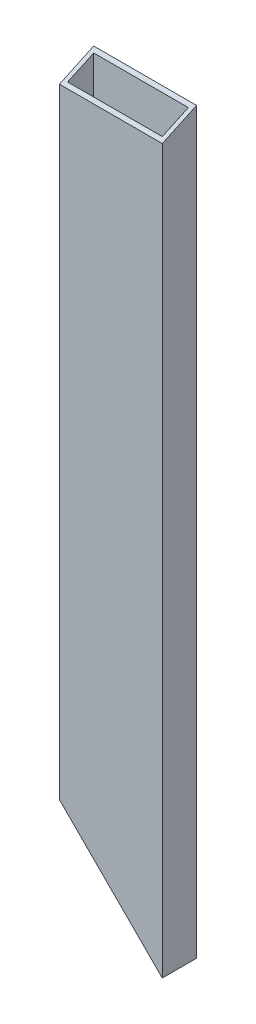
SolidWorks part; units mm, degrees
note: '?' marks a value the reader was unsure of.
material "A500"
ref_plane "Front Plane" through (0, 0, 0) normal (0, 0, 1) x (1, 0, 0)
ref_plane "Top Plane" through (0, 0, 0) normal (0, 1, 0) x (1, 0, 0)
ref_plane "Right Plane" through (0, 0, 0) normal (1, 0, 0) x (0, 0, -1)
sketch "Sketch1" plane through (0, 0, 0) normal (0, 1, 0) x (1, 0, 0)
  line L0 (0, 9.652) -> (0, 12.7) construction
  line L1 (-38.1, 12.7) -> (38.1, 12.7)
  line L2 (-38.1, 12.7) -> (-38.1, -12.7)
  line L3 (-38.1, -12.7) -> (38.1, -12.7)
  line L4 (38.1, 12.7) -> (38.1, -12.7)
  line L5 (-35.052, 9.652) -> (35.052, 9.652)
  line L6 (-35.052, 9.652) -> (-35.052, -9.652)
  line L7 (-35.052, -9.652) -> (35.052, -9.652)
  line L8 (35.052, 9.652) -> (35.052, -9.652)
  line L9 (35.052, 0) -> (38.1, 0) construction
  line L10 (0, -9.652) -> (0, -12.7) construction
  line L11 (-35.052, 0) -> (-38.1, 0) construction
  line L12 (0, 9.652) -> (0, 0) construction
  line L13 (0, 0) -> (-35.052, 0) construction
  dimension "D1" = 76.2
  dimension "D2" = 25.4
  dimension "D3" = 3.048
extrude "Boss-Extrude1" add sketch "Sketch1" along normal up to vertex (503 mm away)
ref_plane "Plane1" through (0, 0, 0) normal (0, 0, 1) x (1, 0, 0)
sketch "Sketch2" plane through (0, 0, 0) normal (0, 0, 1) x (1, 0, 0)
  line L0 (0, 0) -> (0, 503) construction
  line L1 (-38.1, 503) -> (38.1, 503) construction
  line L2 (0, 251.5) -> (-38.1, 251.5) construction
  line L3 (-38.1, 503) -> (-38.1, 0) construction
  line L4 (0, 251.5) -> (38.1, 251.5) construction
  line L5 (38.1, 503) -> (38.1, 0) construction
ref_axis "Axis1" through (0, 503, 0) along (0, -1, 0)?
sketch "Sketch3" plane through (0, 0, 0) normal (0, -1, 0) x (1, 0, 0)
  line L0 (35.052, 9.652) -> (35.052, -9.652) construction
  line L1 (35.052, 9.652) -> (35.052, -9.652)
  line L2 (35.052, -9.652) -> (-35.052, -9.652) construction
  line L3 (35.052, -9.652) -> (-35.052, -9.652)
  line L4 (-38.1, 12.7) -> (-38.1, -12.7)
  line L5 (-38.1, -12.7) -> (38.1, -12.7)
  line L6 (38.1, -12.7) -> (38.1, 12.7)
  line L7 (38.1, 12.7) -> (-38.1, 12.7)
  line L8 (-38.1, 12.7) -> (-38.1, -12.7)
  line L9 (-38.1, -12.7) -> (38.1, -12.7)
  line L10 (38.1, -12.7) -> (38.1, 12.7)
  line L11 (38.1, 12.7) -> (-38.1, 12.7)
  line L12 (-35.052, 9.652) -> (35.052, 9.652) construction
  line L13 (-35.052, 9.652) -> (35.052, 9.652)
  line L14 (-35.052, -9.652) -> (-35.052, 9.652) construction
  line L15 (-35.052, -9.652) -> (-35.052, 9.652)
  dimension "D1" = 0
extrude "Boss-Extrude2" add sketch "Sketch3" along normal blind 38.1
sketch "Sketch4" plane through (0, 503, 0) normal (0, 1, 0) x (1, 0, 0)
  line L0 (35.052, -9.652) -> (35.052, 9.652) construction
  line L1 (35.052, -9.652) -> (35.052, 9.652)
  line L2 (-35.052, -9.652) -> (35.052, -9.652) construction
  line L3 (-35.052, -9.652) -> (35.052, -9.652)
  line L4 (-38.1, 12.7) -> (-38.1, -12.7)
  line L5 (-38.1, -12.7) -> (38.1, -12.7)
  line L6 (38.1, -12.7) -> (38.1, 12.7)
  line L7 (38.1, 12.7) -> (-38.1, 12.7)
  line L8 (-38.1, 12.7) -> (-38.1, -12.7)
  line L9 (-38.1, -12.7) -> (38.1, -12.7)
  line L10 (38.1, -12.7) -> (38.1, 12.7)
  line L11 (38.1, 12.7) -> (-38.1, 12.7)
  line L12 (35.052, 9.652) -> (-35.052, 9.652) construction
  line L13 (35.052, 9.652) -> (-35.052, 9.652)
  line L14 (-35.052, 9.652) -> (-35.052, -9.652) construction
  line L15 (-35.052, 9.652) -> (-35.052, -9.652)
  dimension "D1" = 0
sketch "Sketch5" plane through (0, 0.0477, 0) normal (0, 0, -1) x (0, -1, 0)
  line L0 (-54.5398, 54.4851) -> (43.4084, -43.2794)
  line L1 (0, 25.4) -> (-54.5398, 54.4851) construction
  line L2 (0, 500) -> (0, 0) construction
  line L3 (-54.5398, 54.4851) -> (-25.3523, 0) construction
  line L4 (0.0477, 0) -> (-502.9523, 0) construction
  line L6 (-54.5398, 54.4851) -> (36.5906, 145.7868)
  line L7 (36.5906, 145.7868) -> (134.5388, 48.0222)
  line L8 (134.5388, 48.0222) -> (43.4084, -43.2794)
  dimension "D1" = 25.4
  dimension "D2" = 25.4
extrude "Cut-Extrude1" cut sketch "Sketch5" against normal through all both and the other way through all
extrude "Boss-Extrude3" add sketch "Sketch4" along normal blind 38.1
sketch "Sketch7" plane through (38.1, 0, 0) normal (1, 0, 0) x (0, 0, -1)
  line L3 (0, 503) -> (-19.7823, 519.7329) construction
  line L4 (0, 503) -> (-152.7, 632.1616) construction
  line L5 (0, 503) -> (0, 477.0899) construction
  line L6 (0, 0) -> (0, 503) construction
  line L7 (0, 477.0899) -> (0, 503) construction
  line L8 (0, 503) -> (-33.8727, 487.2863)
  line L9 (0, 503) -> (-19.7823, 519.7329) construction
  line L14 (-33.8727, 487.2863) -> (-19.7823, 519.7329) construction
  line L15 (-33.8727, 487.2863) -> (0, 477.0899) construction
  line L16 (0, 503) -> (53.5924, 527.8618)
  line L17 (53.5924, 527.8618) -> (15.9068, 602.5414)
  line L18 (15.9068, 602.5414) -> (-33.9677, 580.6727)
  line L19 (-33.9677, 580.6727) -> (-33.8727, 487.2863)
extrude "Cut-Extrude4" cut sketch "Sketch7" against normal through all
equation "\"tubeMainWidth\"= 76.2mm"
equation "\"tubeSecondWidth\"= 25.4mm"
equation "\"tubeThickness\"= 3.048mm"
equation "\"halfMainWidthOfTubing\"= (\"tubeMainWidth\"/2)"
equation "\"D1@Sketch1\"=\"tubeMainWidth\""
equation "\"D2@Sketch1\"=\"tubeSecondWidth\""
equation "\"D3@Sketch1\"=\"tubeThickness\""
equation "\"D1@Boss-Extrude2\"=\"halfMainWidthOfTubing\""
equation "\"D1@Boss-Extrude3\"=\"halfMainWidthOfTubing\""
